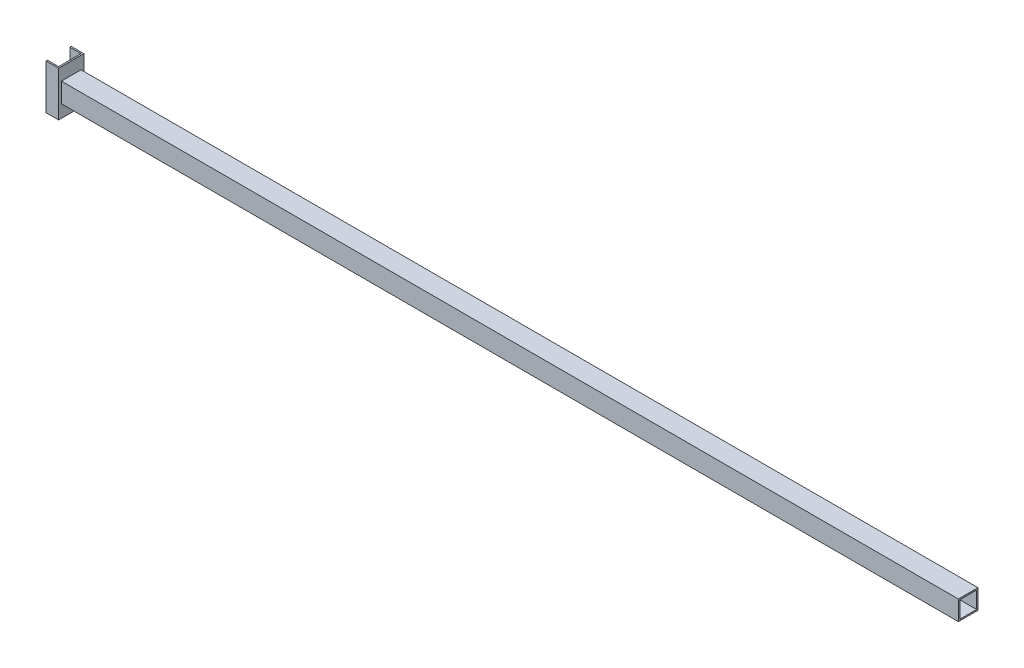
SolidWorks part; units mm, degrees
note: The reader was unsure of these and kept them because the rebuilt part matched: shared geometry of "Sketch1<3>", "Sketch1<4>".
material "6061-T4 (SS)"
ref_plane "Front Plane" through (0, 0, 0) normal (0, 0, 1) x (1, 0, 0)
ref_plane "Top Plane" through (0, 0, 0) normal (0, 1, 0) x (1, 0, 0)
ref_plane "Right Plane" through (0, 0, 0) normal (1, 0, 0) x (0, 0, -1)
sketch "Sketch1" plane through (0, 0, 0) normal (1, 0, 0) x (0, 0, -1)
  line L0 (-12.7, 25.4) -> (-12.7, -25.4)
  line L1 (-14.2875, -25.4) -> (14.2875, -25.4)
  line L2 (-14.2875, -25.4) -> (-14.2875, 25.4)
  line L3 (-14.2875, 25.4) -> (14.2875, 25.4)
  line L4 (14.2875, -25.4) -> (14.2875, 25.4)
  line L5 (-14.2875, -25.4) -> (14.2875, 25.4) construction
  line L6 (-14.2875, 25.4) -> (14.2875, -25.4) construction
  line L7 (12.7, 25.4) -> (12.7, -25.4)
  line L8 (-9.525, 9.525) -> (9.525, 9.525)
  line L9 (-11.1125, -11.1125) -> (11.1125, -11.1125)
  line L10 (-11.1125, -11.1125) -> (-11.1125, 11.1125)
  line L11 (-11.1125, 11.1125) -> (11.1125, 11.1125)
  line L12 (11.1125, -11.1125) -> (11.1125, 11.1125)
  line L13 (-11.1125, -11.1125) -> (11.1125, 11.1125) construction
  line L14 (-11.1125, 11.1125) -> (11.1125, -11.1125) construction
  line L15 (9.525, -9.525) -> (9.525, 9.525)
  line L16 (-9.525, -9.525) -> (9.525, -9.525)
  line L17 (-9.525, -9.525) -> (-9.525, 9.525)
  point P0 (0, 0)
  point P10 (0, 0)
  dimension "D1" = 50.8
  dimension "D2" = 28.575
  dimension "D3" = 1.5875
  dimension "D4" = 1.5875
  dimension "D5" = 22.225
  dimension "D6" = 22.225
  dimension "D7" = 1.5875
extrude "Boss-Extrude1" add sketch "Sketch1" against normal blind 1.5875 contours L0 L11 L7 L3 | L11 L0 L9 L7 | L9 L0 L1 L7 | L3 L2 L1 L0 | L3 L7 L1 L4 | L17 L16 L15 L8
extrude "Boss-Extrude2" add sketch "Sketch1<3>" against normal blind 14.2875 contours L3 L2 L1 L0 | L3 L7 L1 L4
sketch "Sketch1<3>" plane through (0, 0, 0) normal (1, 0, 0) x (0, 0, -1) same geometry as "Sketch1"
extrude "Boss-Extrude3" add sketch "Sketch1<4>" along normal blind 1016 contours L11 L0 L9 L7 L16 L17 L8 L15
sketch "Sketch1<4>" plane through (0, 0, 0) normal (1, 0, 0) x (0, 0, -1) same geometry as "Sketch1"
sketch3d "3DSketch1"
  line L0 (-1.5875, 25.4, 0) -> (-1.5875, -25.4, 0) construction
  line L1 (-1.5875, 25.4, 12.7) -> (-1.5875, 25.4, -12.7) construction
  line L2 (-1.5875, -25.4, 12.7) -> (-1.5875, -25.4, -12.7) construction
  line L5 (-1.5875, 12.7, -6.35) -> (-4.7625, 12.7, -6.35)
  line L6 (-4.7625, 12.7, -6.35) -> (-1.5875, 19.05, -6.35)
  line L7 (-1.5875, 19.05, -6.35) -> (-1.5875, 12.7, -6.35)
  dimension "D1" = 6.35
  dimension "D2" = 6.35
  dimension "D3" = 6.35
  dimension "D4" = 3.175
extrude "Boss-Extrude4" add sketch "3DSketch1" along a picked direction on the side of the normal blind 12.7
pattern_linear "LPattern1" count 2 spacing 25.4 along (0, -1, 0) of "Boss-Extrude4"
